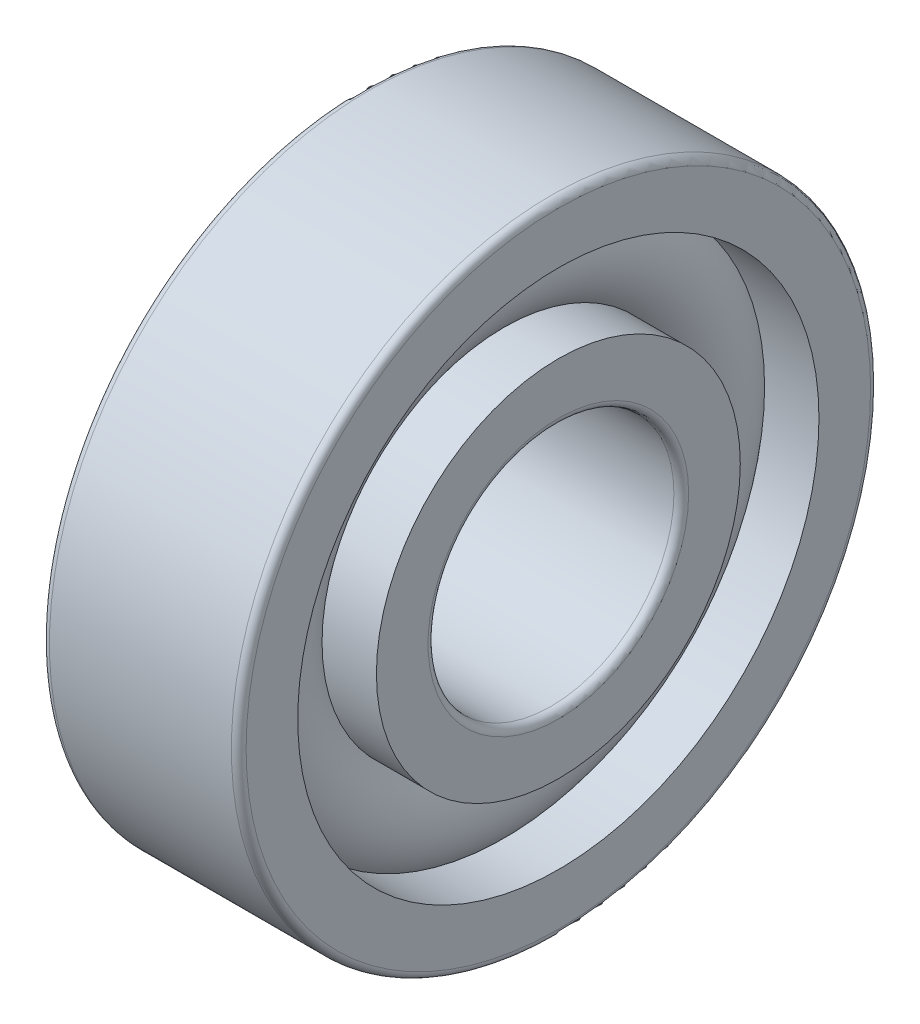
SolidWorks part; units mm, degrees
material "Aço cromo inoxidável"
ref_plane "Plane1" through (0, 0, 0) normal (0, 0, 1) x (1, 0, 0)
ref_plane "Plane2" through (0, 0, 0) normal (0, 1, 0) x (1, 0, 0)
ref_plane "Plane3" through (0, 0, 0) normal (1, 0, 0) x (0, 0, -1)
sketch "Clipboard" plane through (0, 0, 0) normal (0, 0, 1) x (1, 0, 0)
  line L0 (-10, 0) -> (10, 0) construction
  line L1 (0, 0) -> (22.3471, -0.7804)
  line L2 (0, 0) -> (8.9945, 0.3141)
  line L3 (0, 0) -> (22.3471, -0.7804)
  line L4 (0, 0) -> (-22.3573, -0.3902)
  dimension "BallCLRad" = 9
  dimension "Count" = 2
  dimension "Show_count" = 2
  dimension "Max_count" = 2
  dimension "Min_count" = 1
sketch "CagSpiSke" plane through (0, 0, 0) normal (0, 0, 1) x (1, 0, 0)
  line L0 (0.24, 8.6) -> (0.24, 9.4)
  line L1 (0.24, 9.4) -> (-0.24, 9.4)
  line L2 (-0.24, 9.4) -> (-0.24, 8.6)
  line L3 (-0.24, 8.6) -> (0.24, 8.6)
  line L4 (-20.6375, 0) -> (20.6375, 0) construction
  line L5 (0, 0) -> (0, 23.7692) construction
  dimension "Thickness" = 0.48
  dimension "OD" = 18.8
  dimension "ID" = 17.2
revolve "CageSpine" add sketch "CagSpiSke" angle 0.001 about L4 reverse direction yes
ref_axis "Axis1" through (-50, 0, 0) along (1, 0, 0)
sketch "CagBalSke" plane through (0, 0, 0) normal (0, 0, 1) x (1, 0, 0)
  line L0 (-2.64, 9) -> (2.64, 9)
  line L1 (-1.905, 9) -> (1.905, 9) construction
  line L2 (-10, 0) -> (10, 0) construction
  line L3 (0, 0) -> (0, 24) construction
  arc A0 (2.64, 9) -> (-2.64, 9) centre (0, 9) cw
  dimension "CageWallOD" = 5.28
  dimension "BallCLRad" = 9
revolve "CageBall" [suppressed] add sketch "CagBalSke" angle 360 about L1 reverse direction yes
pattern_circular "CageBalls" [suppressed] count 2 every 180 about axis through (-50, 0, 0) along (1, 0, 0)
sketch "CagTrmODSke" plane through (0, 0, 0) normal (0, 0, 1) x (1, 0, 0)
  line L0 (2.641, 9.4) -> (2.641, 11.641)
  line L1 (2.641, 11.641) -> (-2.641, 11.641)
  line L2 (-2.641, 11.641) -> (-2.641, 9.4)
  line L3 (-2.641, 9.4) -> (2.641, 9.4)
  line L4 (-20.6375, 0) -> (20.6375, 0) construction
  line L5 (0, 0) -> (0, 25) construction
  dimension "Width" = 5.282
  dimension "ID" = 18.8
  dimension "OD" = 23.282
revolve "CageTrimOD" [suppressed] cut sketch "CagTrmODSke" angle 360 about L4 reverse direction yes
sketch "CagTrmIDSke" plane through (0, 0, 0) normal (0, 0, 1) x (1, 0, 0)
  line L0 (2.641, 6.361) -> (2.641, 8.6)
  line L1 (2.641, 8.6) -> (-2.641, 8.6)
  line L2 (-2.641, 8.6) -> (-2.641, 6.361)
  line L3 (-2.641, 6.361) -> (2.641, 6.361)
  line L4 (-20.6375, 0) -> (20.6375, 0) construction
  line L5 (0, 0) -> (0, 25) construction
  dimension "ID" = 12.722
  dimension "OD" = 17.2
  dimension "Width" = 5.282
revolve "CageTrimID" [suppressed] cut sketch "CagTrmIDSke" angle 360 about L4 reverse direction yes
sketch "BalSimSke" plane through (0, 0, 0) normal (0, 0, 1) x (1, 0, 0)
  line L0 (-10, 0) -> (10, 0) construction
  line L1 (-10, 9) -> (10, 9) construction
  line L2 (0, 0) -> (0, 23) construction
  circle A0 centre (0, 9) radius 2.4
  dimension "Ball_diameter" = 4.8
  dimension "BallCLRad" = 9
revolve "BallsSimplified" add sketch "BalSimSke" angle 360 about L0
sketch "BalDetSke" plane through (0, 0, 0) normal (0, 0, 1) x (1, 0, 0)
  line L0 (-2.4, 9) -> (2.4, 9)
  line L1 (-1.905, 9) -> (1.905, 9) construction
  line L2 (0, 0) -> (0, 25) construction
  arc A0 (2.4, 9) -> (-2.4, 9) centre (0, 9) cw
  dimension "Ball_diameter" = 4.8
  dimension "BallCLRad" = 9
revolve "BallDetailed" [suppressed] add sketch "BalDetSke" angle 360 about L1 reverse direction yes
sketch "InnRacSke" plane through (0, 0, 0) normal (0, 0, 1) x (1, 0, 0)
  line L0 (-1.7552, 7.4) -> (-4, 7.4)
  line L1 (-4, 7.4) -> (-4, 5.3)
  line L2 (-3.7, 5) -> (3.7, 5)
  line L3 (4, 5.3) -> (4, 7.4)
  line L4 (4, 7.4) -> (1.7552, 7.4)
  line L5 (-20.6375, 0) -> (20.6375, 0) construction
  line L6 (0, 0) -> (0, 30) construction
  arc A0 (-4, 5.3) -> (-3.7, 5) centre (-3.7, 5.3) ccw
  arc A1 (3.7, 5) -> (4, 5.3) centre (3.7, 5.3) ccw
  arc A2 (1.7552, 7.4) -> (-1.7552, 7.4) centre (0, 9) cw
  dimension "Fillet_radius" = 0.3
  dimension "Ball_diameter" = 4.75
  dimension "ID" = 10
  dimension "OD" = 14.8
  dimension "Width" = 8
  dimension "BallCLRad" = 9
revolve "InnerRace" add sketch "InnRacSke" angle 360 about L5 reverse direction yes
sketch "OutRacSke" plane through (0, 0, 0) normal (0, 0, 1) x (1, 0, 0)
  line L0 (-1.7552, 10.6) -> (-4, 10.6)
  line L1 (-4, 10.6) -> (-4, 12.7)
  line L2 (-3.7, 13) -> (3.7, 13)
  line L3 (4, 12.7) -> (4, 10.6)
  line L4 (4, 10.6) -> (1.7552, 10.6)
  line L5 (-20.6375, 0) -> (20.6375, 0) construction
  line L6 (0, 0) -> (0, 30) construction
  arc A0 (-4, 12.7) -> (-3.7, 13) centre (-3.7, 12.7) cw
  arc A1 (3.7, 13) -> (4, 12.7) centre (3.7, 12.7) cw
  arc A2 (1.7552, 10.6) -> (-1.7552, 10.6) centre (0, 9) ccw
  dimension "Fillet_radius" = 0.3
  dimension "Ball_diameter" = 4.75
  dimension "OD" = 26
  dimension "ID" = 21.2
  dimension "Width" = 8
  dimension "BallCLRad" = 9
revolve "OuterRace" add sketch "OutRacSke" angle 360 about L5 reverse direction yes
pattern_circular "BallsDetailed" [suppressed] count 2 every 180 about axis through (-50, 0, 0) along (1, 0, 0)
equation "\"BallCLRad@Clipboard\" = ( \"OD@OutRacSke\" + \"ID@InnRacSke\" ) / 4"
equation "\"BallCLRad@BalSimSke\" = \"BallCLRad@Clipboard\""
equation "\"BallCLRad@BalDetSke\" = \"BallCLRad@Clipboard\""
equation "\"BallCLRad@InnRacSke\" = \"BallCLRad@Clipboard\""
equation "\"BallCLRad@OutRacSke\" = \"BallCLRad@Clipboard\""
equation "\"Ball_diameter@InnRacSke\" = \"Ball_diameter@BalDetSke\" - 0.05"
equation "\"Ball_diameter@OutRacSke\" = \"Ball_diameter@BalDetSke\" - 0.05"
equation "\"Ball_diameter@BalSimSke\" = \"Ball_diameter@BalDetSke\""
equation "\"Width@OutRacSke\" = \"Width@InnRacSke\""
equation "\"Fillet_radius@OutRacSke\" = \"Fillet_radius@InnRacSke\""
equation "\"Max_count@Clipboard\" = int( 3.14159265 / atn(( \"Ball_diameter@BalDetSke\" / 2) / sqr( \"BallCLRad@Clipboard\"  *  \"BallCLRad@Clipboard\" - ( \"Ball_diameter@BalDetSke\" / 2) *  ( \"Ball_diameter@BalDetSke\" / 2))))"
equation "\"Max_count@Clipboard\" = ((sgn( \"Max_count@Clipboard\" - \"Count@Clipboard\" )-1)*( \"Max_count@Clipboard\" - \"Count@Clipboard\" ))/-2+ \"Count@Clipboard\""
equation "\"Count@BallsDetailed\" = int( \"Show_count@Clipboard\" ) "
equation "\"Count@BallsDetailed\" = ((sgn( \"Count@BallsDetailed\" - \"Max_count@Clipboard\" )-1)*( \"Count@BallsDetailed\" - \"Max_count@Clipboard\" ))/-2+ \"Max_count@Clipboard\""
equation "\"Count@BallsDetailed\" = ((sgn( \"Count@BallsDetailed\" - \"Min_count@Clipboard\" )+1)*( \"Count@BallsDetailed\" - \"Min_count@Clipboard\"))/2 +\"Min_count@Clipboard\""
equation "\"Angle@BallsDetailed\" = 360.0 / \"Max_count@Clipboard\""
equation "\"BallCLRad@CagBalSke\" = \"BallCLRad@Clipboard\""
equation "\"Count@CageBalls\" = \"Count@BallsDetailed\""
equation "\"Angle@CageBalls\" = \"Angle@BallsDetailed\""
equation "\"Angle@CageSpine\" =  \"Angle@CageBalls\" * ( \"Count@CageBalls\" -1 + int( \"Count@CageBalls\" / \"Max_count@Clipboard\" ) )  + 0.001 -  int( \"Count@CageBalls\" / \"Max_count@Clipboard\" ) * 0.001"
equation "\"Angle@CageSpine\" =  \"Angle@CageSpine\" * int( \"Min_count@Clipboard\" / 2) + int(1 / \"Min_count@Clipboard\")  * 0.001"
equation "\"CageWallOD@CagBalSke\" =  \"Ball_diameter@BalDetSke\" * 1.1"
equation "\"Thickness@CagSpiSke\" =  \"Ball_diameter@BalDetSke\" * 0.1"
equation "\"OD@CagTrmODSke\" = \"BallCLRad@Clipboard\" * 2 + \"CageWallOD@CagBalSke\" + 0.002"
equation "\"ID@CagTrmODSke\" = \"BallCLRad@Clipboard\" * 2 + \"Ball_diameter@BalDetSke\" / 6"
equation "\"OD@CagTrmIDSke\" = \"BallCLRad@Clipboard\" * 2 - \"Ball_diameter@BalDetSke\" / 6"
equation "\"ID@CagTrmIDSke\" = \"BallCLRad@Clipboard\" * 2 - \"CageWallOD@CagBalSke\" + 0.002"
equation "\"OD@CagSpiSke\" = \"ID@CagTrmODSke\""
equation "\"ID@CagSpiSke\" = \"OD@CagTrmIDSke\""
equation "\"Width@CagTrmODSke\" = \"CageWallOD@CagBalSke\" + 0.002"
equation "\"Width@CagTrmIDSke\" = \"CageWallOD@CagBalSke\" + 0.002"
